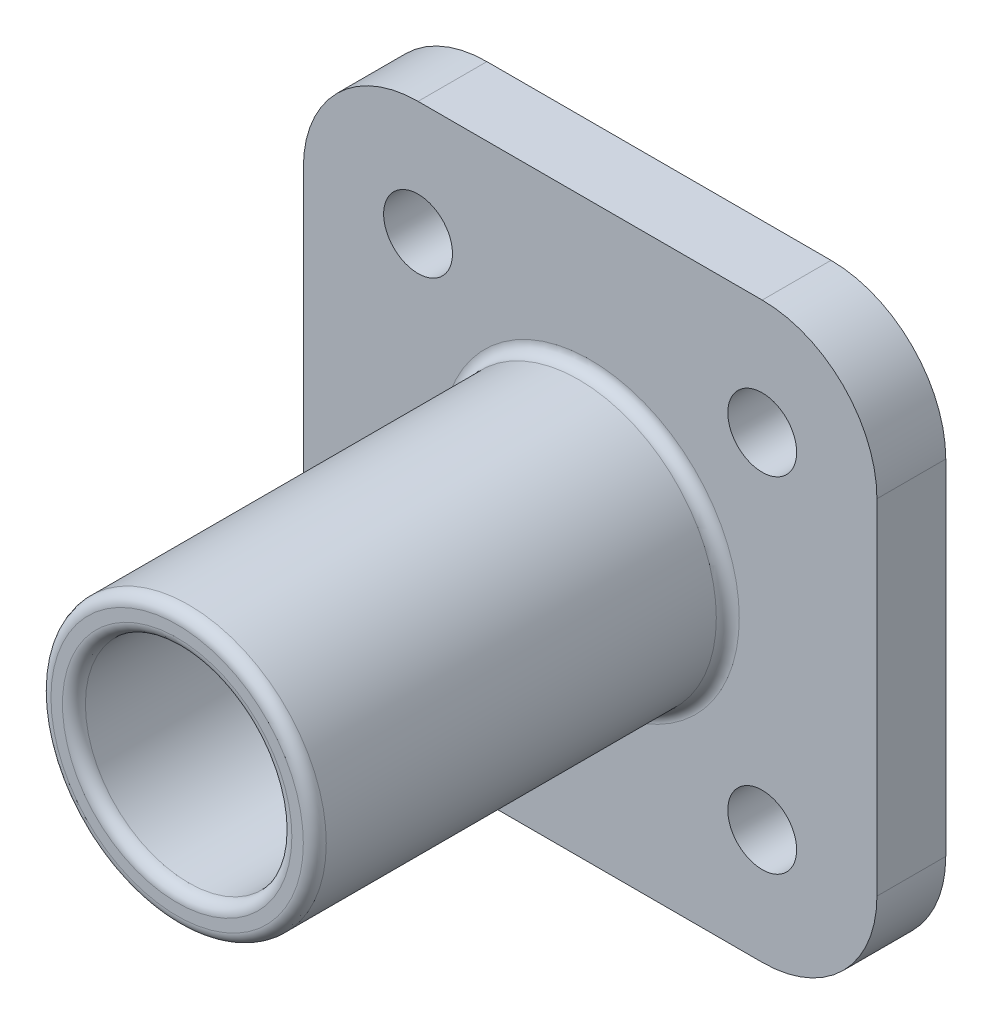
SolidWorks part; units mm, degrees
ref_plane "Plan de face" through (0, 0, 0) normal (0, 0, 1) x (1, 0, 0)
ref_plane "Plan de dessus" through (0, 0, 0) normal (0, 1, 0) x (1, 0, 0)
ref_plane "Plan de droite" through (0, 0, 0) normal (1, 0, 0) x (0, 0, -1)
sketch "Esquisse1" plane through (0, 0, 0) normal (0, 0, 1) x (1, 0, 0)
  line L0 (-7.5, 7.5) -> (7.5, 7.5) construction
  line L1 (7.5, -12.5) -> (-7.5, -12.5)
  line L2 (12.5, -7.5) -> (12.5, 7.5)
  line L3 (7.5, 12.5) -> (-7.5, 12.5)
  line L4 (-12.5, -7.5) -> (-12.5, 7.5)
  line L5 (12.5, -12.5) -> (-12.5, 12.5) construction
  line L6 (12.5, 12.5) -> (-12.5, -12.5) construction
  line L7 (-7.5, 7.5) -> (-7.5, -7.5) construction
  arc A0 (7.5, -12.5) -> (12.5, -7.5) centre (7.5, -7.5) ccw
  arc A1 (-7.5, -12.5) -> (-12.5, -7.5) centre (-7.5, -7.5) cw
  arc A2 (12.5, 7.5) -> (7.5, 12.5) centre (7.5, 7.5) ccw
  arc A3 (-7.5, 12.5) -> (-12.5, 7.5) centre (-7.5, 7.5) ccw
  circle A4 centre (-7.5, 7.5) radius 1.5
  circle A5 centre (7.5, 7.5) radius 1.5
  circle A6 centre (7.5, -7.5) radius 1.5
  circle A7 centre (-7.5, -7.5) radius 1.5
  point P0 (0, 0)
  dimension "D2" = 5
  dimension "D3" = 3
  dimension "D1" = 25
  dimension "D4" = 2
  dimension "D5" = 2
extrude "Boss.-Extru.1" add sketch "Esquisse1" along normal blind 3
sketch "Esquisse2" plane through (0, 0, 3) normal (0, 0, 1) x (1, 0, 0)
  circle A0 centre (0, 0) radius 6
  circle A1 centre (0, 0) radius 4.5
  dimension "D1" = 9
  dimension "D2" = 12
extrude "Boss.-Extru.2" add sketch "Esquisse2" along normal blind 18 contours A0 | A1
fillet "Congé1" radius 0.5 3 edges at (6, 0, 3) (6, 0, 21) (4.5, 0, 21)
